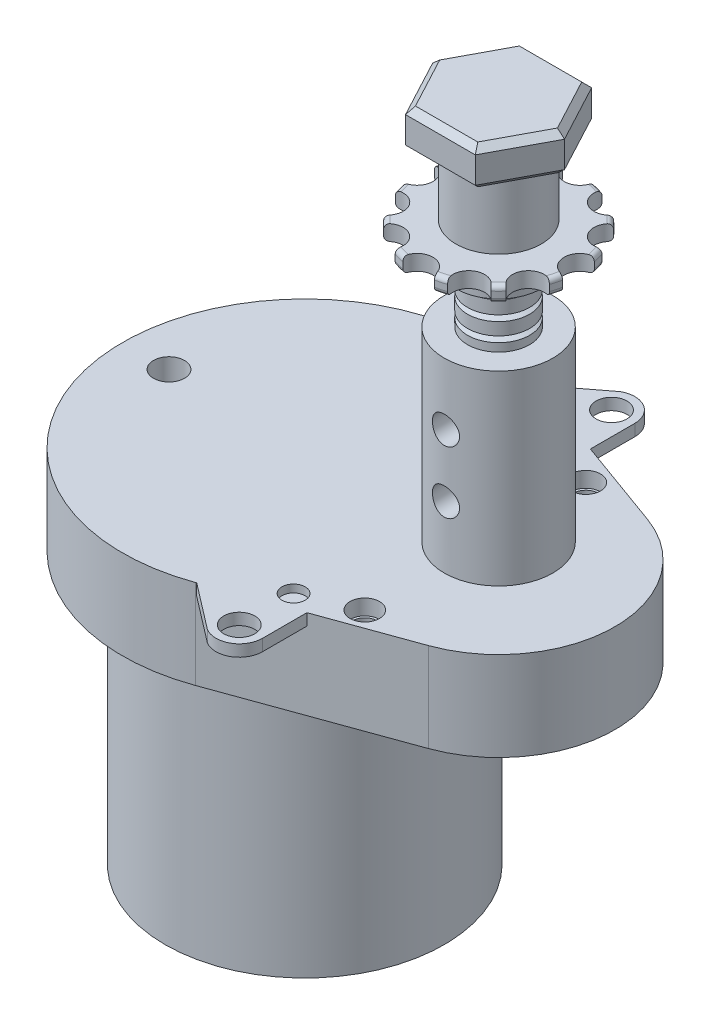
SolidWorks part; units mm, degrees
ref_plane "Front Plane" through (0, 0, 0) normal (0, 0, 1) x (1, 0, 0)
ref_plane "Top Plane" through (0, 0, 0) normal (0, 1, 0) x (1, 0, 0)
ref_plane "Right Plane" through (0, 0, 0) normal (1, 0, 0) x (0, 0, -1)
sketch "Sketch1" plane through (0, 0, 0) normal (0, 1, 0) x (1, 0, 0)
  circle A0 centre (0, 0) radius 18
  dimension "D1" = 36
extrude "Boss-Extrude1" add sketch "Sketch1" along normal blind 34
sketch "Sketch2" plane through (0, 34, 0) normal (0, 1, 0) x (1, 0, 0)
  circle A0 centre (0, 0) radius 17
  dimension "D1" = 34
extrude "Boss-Extrude2" add sketch "Sketch2" along normal blind 1
sketch "Sketch3" plane through (0, 35, 0) normal (0, 1, 0) x (1, 0, 0)
  line L0 (0, 0) -> (25, 0)
  line L1 (30.1, 14.1064) -> (7.99, 22.1)
  line L2 (30.1, -14.1064) -> (7.99, -22.1)
  circle A0 centre (0, 0) radius 23.5
  circle A1 centre (25, 0) radius 15
  circle M5 centre (0, 0) radius 17
  dimension "D1" = 47
  dimension "D2" = 30
  dimension "D3" = 25
extrude "Boss-Extrude3" add sketch "Sketch3" along normal blind 11.5 contours A1 A0 M5 | A1 A0 | A1 A0 | A0 A1 L0 M5 | A1 A0 L0 M5 | A1 L0 M5 | L0 A1 M5 | A1 M5 | A1 A0 region at (19.0654, 35, -6.2917) region at (13.5463, 35, 3.7961) region at (13.5463, 35, -3.7961) region at (19.0654, 35, 6.2917) region at (29.7017, 35, 0) region at (-1.5871, 35, 0) region at (-17.634, 35, 0) region at (19.2987, 35, -16.7392) region at (19.2987, 35, 16.7392)
sketch "Sketch4" plane through (0, 46.5, 0) normal (0, 1, 0) x (1, 0, 0)
  circle A1 centre (25, 0) radius 4
  dimension "D2" = 8
extrude "Boss-Extrude5" add sketch "Sketch4" along normal blind 2
sketch "Sketch5" plane through (0, 48.5, 0) normal (0, 1, 0) x (1, 0, 0)
  circle A0 centre (25, 0) radius 7
  dimension "D1" = 14
extrude "Boss-Extrude6" add sketch "Sketch5" along normal blind 24
sketch "Sketch7" plane through (0, 72.5, 0) normal (0, 1, 0) x (1, 0, 0)
  circle A0 centre (25, 0) radius 4
  dimension "D1" = 8
extrude "Boss-Extrude7" add sketch "Sketch7" along normal blind 7
sketch "Sketch8" plane through (0, 79.5, 0) normal (0, 1, 0) x (1, 0, 0)
  circle A0 centre (25, 0) radius 5.5
  dimension "D1" = 11
extrude "Boss-Extrude8" add sketch "Sketch8" along normal blind 14
sketch "Sketch9" plane through (0, 0, 0) normal (0, 0, 1) x (1, 0, 0)
  line L0 (19.5117, 79.5) -> (30.5, 79.5)
  line L1 (19.5, 79.5) -> (30.5, 79.5) construction
  line L2 (30.5, 79.5) -> (30.5, 82.5)
  line L3 (30.5, 79.5) -> (30.5, 93.5) construction
  line L4 (30.5, 82.5) -> (19.5, 82.5)
  line L5 (19.5, 93.5) -> (19.5, 79.5) construction
  line L6 (19.5, 82.5) -> (19.5117, 79.5)
  line L7 (19.5, 82.5) -> (19.5, 84.5)
  line L8 (19.5, 84.5) -> (30.5, 84.5)
  line L9 (30.5, 84.5) -> (30.5, 82.5)
  line L10 (19.5, 84.5) -> (14.5, 84.5)
  line L11 (14.5, 84.5) -> (14.5, 82.5)
  line L12 (14.5, 82.5) -> (19.5, 82.5)
  line L13 (25.0059, 79.5) -> (25.0059, 88.8611)
  dimension "D1" = 3
  dimension "D2" = 2
  dimension "D3" = 5
revolve "Revolve1" add sketch "Sketch9" angle 360 about L13 region at (17, 83.5, 0)
fillet "Fillet1" radius 0.6 1 edges at (25.0059, 84.5, -10.5059)
fillet "Fillet2" radius 0.6 1 edges at (25.0059, 82.5, -10.5059)
sketch "Sketch10" plane through (0, 84.5, 0) normal (0, 1, 0) x (1, 0, 0)
  circle A0 centre (25.0059, 0) radius 11
  circle A1 centre (25.0059, 10.505) radius 2.05
  circle M2 centre (25.0059, 0) radius 9.9059
  dimension "D1" = 4.1
  dimension "D2" = 22
  dimension "D3" = 10.505
extrude "Cut-Extrude1" cut sketch "Sketch10" against normal blind 14 contours A1 M2 | A1 A0 M2 region at (25.0059, 84.5, -10.3938) region at (25.0059, 84.5, -9.2695)
pattern_circular "CirPattern1" count 12 over 360 about axis through (25, 93.5, 0) along (0, 1, 0) of "Cut-Extrude1"
sketch "Sketch11" plane through (0, 93.5, 0) normal (0, 1, 0) x (1, 0, 0)
  line L0 (25, 0) -> (16.5, 0)
  line L1 (25, 0) -> (33.5, 0)
  line L2 (29.5, 7.5) -> (20.5, 7.5)
  line L3 (25, 0) -> (25, 13.7265) construction
  line L4 (29.5, -7.5) -> (20.5, -7.5)
  line L5 (20.5, 7.5) -> (16.5, 0)
  line L6 (20.5, -7.5) -> (16.5, 0)
  line L7 (29.5, -7.5) -> (33.5, 0)
  line L8 (29.5, 7.5) -> (33.5, 0)
  circle A0 centre (25, 0) radius 7.5
  point P10 (25, 7.5)
  circle M6 centre (25, 0) radius 5.5
  dimension "D1" = 15
  dimension "D2" = 8.5
  dimension "D3" = 8.5
  dimension "D4" = 4.5
extrude "Boss-Extrude10" add sketch "Sketch11" along normal blind 5 contours A0 L2 L5 | A0 L8 L2 | A0 L5 L0 | L3 A0 L0 M6 | L3 L1 A0 M6 | A0 L1 L8 | A0 L7 L1 | A0 L1 L0 M6 | A0 L6 L4 | A0 L0 L6 | A0 L4 L7 | L3 L1 M6 | L0 L3 M6 | L1 L0 M6 region at (25, 93.5, 2.3343) region at (27.3343, 93.5, -2.3343) region at (22.6657, 93.5, -2.3343) region at (25, 93.5, 5.6677) region at (20.8293, 93.5, -4.1707) region at (29.1707, 93.5, -4.1707) region at (17.2851, 93.5, 0.9041) region at (17.2851, 93.5, -0.9041) region at (32.7149, 93.5, -0.9041) region at (32.7149, 93.5, 0.9041) region at (21.0015, 93.5, -6.6642) region at (28.9985, 93.5, -6.6642) region at (21.0015, 93.5, 6.6642) region at (28.9985, 93.5, 6.6642)
chamfer "Chamfer1" distance 0.8 angle 45 12 edges at (25, 93.5, 7.5) (18.5, 93.5, 3.75) (18.5, 93.5, -3.75) (25, 93.5, -7.5) (31.5, 93.5, -3.75) (31.5, 93.5, 3.75) (31.5, 98.5, 3.75) (31.5, 98.5, -3.75) (25, 98.5, -7.5) (18.5, 98.5, -3.75) (18.5, 98.5, 3.75) (25, 98.5, 7.5)
sketch "Sketch13" plane through (0, 0, 0) normal (0, 0, 1) x (1, 0, 0)
  line L0 (21, 79.5) -> (29, 79.5)
  line L1 (29, 79.5) -> (29, 72.5)
  line L2 (29, 72.5) -> (21, 72.5)
  line L3 (21, 72.5) -> (21, 79.5)
  line L4 (21, 79.1127) -> (21.9094, 78.7462)
  line L5 (21.9094, 78.7462) -> (21, 78.3593)
  line L6 (21, 78.3593) -> (21, 76.6593)
  line L7 (21, 76.6593) -> (21.9094, 76.2928)
  line L8 (21.9094, 76.2928) -> (21, 75.9059)
  line L9 (21, 75.9059) -> (21, 74.3059)
  line L10 (21, 74.3059) -> (21.9094, 73.9393)
  line L11 (21.9094, 73.9393) -> (21, 73.5524)
  line L12 (25, 72.5) -> (25, 79.5)
  line L13 (21, 76.6593) -> (21, 75.9059)
  line L14 (21, 74.3059) -> (21, 73.5524)
  line L15 (21, 79.1127) -> (21, 78.3593)
  dimension "D1" = 0.3873
  dimension "D3" = 1.6
  dimension "D4" = 1.7
revolve "Cut-Revolve2" cut sketch "Sketch13" angle 360 about L12 region at (21.3031, 78.7394, 0) region at (21.3031, 76.286, 0) region at (21.3031, 73.9325, 0)
sketch "Sketch14" plane through (0, 46.5, 0) normal (0, 1, 0) x (1, 0, 0)
  line L0 (22, 16.5) -> (22, -16.5)
  line L3 (0, 0) -> (40, 0) construction
  circle A0 centre (22, 14.25) radius 2.25
  arc A1 (30.1, -14.1064) -> (30.1, 14.1064) centre (25, 0) ccw construction
  circle A2 centre (22, -14.25) radius 2.25
  circle A3 centre (22, 14.25) radius 1.9
  circle A4 centre (22, -14.25) radius 1.9
  dimension "D2" = 22
  dimension "D3" = 3.8
  dimension "D4" = 4.5
  dimension "D1" = 28.5
extrude "Cut-Extrude3" cut sketch "Sketch14" against normal blind 2 contours L0 A3 | L0 A3 | A4 L0 | A4 L0 region at (22.8064, 46.5, -14.25) region at (21.1936, 46.5, -14.25) region at (22.8064, 46.5, 14.25) region at (21.1936, 46.5, 14.25)
sketch "Sketch15" plane through (0, 44.5, 0) normal (0, 1, 0) x (1, 0, 0)
  circle A0 centre (22, -14.25) radius 1.6
  circle A1 centre (22, 14.25) radius 1.6
  dimension "D1" = 3.2
  dimension "D2" = 3.2
extrude "Cut-Extrude4" cut sketch "Sketch15" against normal blind 12
sketch "Sketch16" plane through (0, 46.5, 0) normal (0, 1, 0) x (1, 0, 0)
  line L0 (15.5628, 19) -> (15.5628, -19.5)
  line L3 (0, 0) -> (50.32, 0) construction
  circle A0 centre (0, 0) radius 23.5
  circle A7 centre (15.5628, 17) radius 2
  circle A8 centre (15.5628, 17) radius 1.5
  circle A9 centre (15.5628, -17) radius 1.5
  circle A10 centre (15.5628, -17) radius 2
  point P18 (22, 14.25)
  dimension "D2" = 2
  dimension "D3" = 3
  dimension "D4" = 7
  dimension "D1" = 34
sketch "Sketch19" plane through (0, 46.5, 0) normal (0, 1, 0) x (1, 0, 0)
  line L0 (-17.5, 0) -> (-23.5, 0)
  line L1 (22, 14.25) -> (22, -14.25)
  circle A0 centre (-17.5, 0) radius 2
  arc A1 (7.99, 22.1) -> (7.99, -22.1) centre (0, 0) ccw construction
  dimension "D1" = 4
  dimension "D2" = 6
extrude "Cut-Extrude13" cut sketch "Sketch16" against normal blind 1 contours A0 A8 L0 | L0 A8 A0 | A0 A8 L0 | L0 A8 A0 | A9 L0 A0 | A9 A0 L0 | A9 A0 L0 | A9 L0 A0 region at (16.3328, 46.5, -17.5452) region at (15.2896, 46.5, -18.1532) region at (16.0511, 46.5, -16.3936) region at (14.8825, 46.5, -16.8613) region at (14.8825, 46.5, 16.8613) region at (15.2896, 46.5, 18.1532) region at (16.3328, 46.5, 17.5452) region at (16.0511, 46.5, 16.3936)
extrude "Cut-Extrude7" cut sketch "Sketch19" against normal blind 11.5 contours A0 region at (-17.5, 46.5, 1.9434)
sketch "Sketch20" plane through (0, 35, 0) normal (0, -1, 0) x (1, 0, 0)
  circle A0 centre (25, 0) radius 7.5
  circle A1 centre (0, 0) radius 18
  circle A2 centre (0, 0) radius 18.5
  dimension "D1" = 15
  dimension "D2" = 36
  dimension "D3" = 37
extrude "Boss-Extrude13" add sketch "Sketch20" along normal blind 4 contours A2 A0 region at (25.1738, 35, 0)
sketch "Sketch21" plane through (0, 31, 0) normal (0, -1, 0) x (1, 0, 0)
  circle A0 centre (25, 0) radius 5
  dimension "D1" = 10
extrude "Cut-Extrude8" cut sketch "Sketch21" against normal blind 0.8
sketch "Sketch22" plane through (0, 31.8, 0) normal (0, -1, 0) x (1, 0, 0)
  circle A0 centre (25, 0) radius 2.25
  circle A1 centre (25, 0) radius 2
  dimension "D1" = 4.5
  dimension "D2" = 4
extrude "Cut-Extrude9" cut sketch "Sketch22" against normal blind 2
sketch "Sketch23" plane through (0, 31.8, 0) normal (0, -1, 0) x (1, 0, 0)
  circle A0 centre (25, 0) radius 2
extrude "Boss-Extrude14" add sketch "Sketch23" along normal blind 0.2
sketch "Sketch24" plane through (0, 35, 0) normal (0, -1, 0) x (1, 0, 0)
  line L0 (0, 0) -> (37.2561, 0) construction
  circle A0 centre (13.944, 17.618) radius 1
  circle A1 centre (13.944, -17.618) radius 1
  dimension "D1" = 2
extrude "Cut-Extrude10" cut sketch "Sketch24" against normal blind 4
sketch "Sketch25" plane through (0, 0, 0) normal (0, 0, 1) x (1, 0, 0)
  line L0 (25, 48.5) -> (25, 72.5) construction
  line L1 (21, 48.5) -> (29, 48.5) construction
  line L2 (32, 72.5) -> (18, 72.5) construction
  circle A0 centre (25, 64.5) radius 1.75
  circle A1 centre (25, 56.5) radius 1.75
  dimension "D3" = 3.5
  dimension "D4" = 3.5
  dimension "D1" = 8
  dimension "D2" = 8
extrude "Cut-Extrude11" cut sketch "Sketch25" against normal blind 4 and the other way blind 1 from offset 4 offset against normal yes
sketch "Sketch26" plane through (0, 0, 0) normal (0, 0, 1) x (1, 0, 0)
  line L0 (25, 72.5) -> (25, 48.5) construction
  line L1 (32, 72.5) -> (18, 72.5) construction
  line L2 (21, 48.5) -> (29, 48.5) construction
  circle A0 centre (25, 64.5) radius 1.75
  circle A1 centre (25, 56.5) radius 1.75
  dimension "D3" = 3.5
  dimension "D4" = 3.5
  dimension "D1" = 8
  dimension "D2" = 8
extrude "Cut-Extrude12" cut sketch "Sketch26" along normal blind 4 from offset 3
sketch "Sketch27" plane through (0, 46.5, 0) normal (0, 1, 0) x (1, 0, 0)
  line L0 (15.5628, 17) -> (15.5628, 24)
  line L1 (0, 0) -> (40, 0)
  line L2 (14.0507, 26.591) -> (-19.1204, 1.1723)
  line L3 (18.5628, 24) -> (18.5628, -24)
  line L4 (14.0507, -26.591) -> (-19.1204, -1.1723)
  line L5 (18.5628, 18.2775) -> (8.1258, 22.0509)
  line L6 (30.1, 14.1064) -> (7.99, 22.1) construction
  line L7 (18.5628, -18.2775) -> (8.1258, -22.0509)
  circle A0 centre (15.5628, 24) radius 2
  circle A1 centre (15.5628, 24) radius 3
  arc A2 (30.1, -14.1064) -> (30.1, 14.1064) centre (25, 0) ccw construction
  circle A3 centre (15.5628, -24) radius 2
  circle A4 centre (15.5628, -24) radius 3
  circle A5 centre (-17.5, 0) radius 2 construction
  point P21 (18.5628, 0)
  line M12 (7.99, -22.1) -> (30.1, -14.1064)
  line M14 (30.1, 14.1064) -> (7.99, 22.1)
  dimension "D2" = 4
  dimension "D3" = 6
  dimension "D1" = 7
extrude "Boss-Extrude15" add sketch "Sketch27" against normal blind 1.5 contours A1 L2 L0 M14 | A1 L0 L3 M14 | A1 L2 A0 | L4 A4 L3 M12 | A4 L4 A3 region at (12.0016, 46.5, -22.1378) region at (17.348, 46.5, -20.2938) region at (13.8078, 46.5, 21.5148) region at (12.8662, 46.5, -22.8925) region at (17.0145, 46.5, 26.528)
sketch "Sketch28" plane through (0, 46.5, 0) normal (0, 1, 0) x (1, 0, 0)
  line L0 (15.5628, 24) -> (15.5628, -24)
